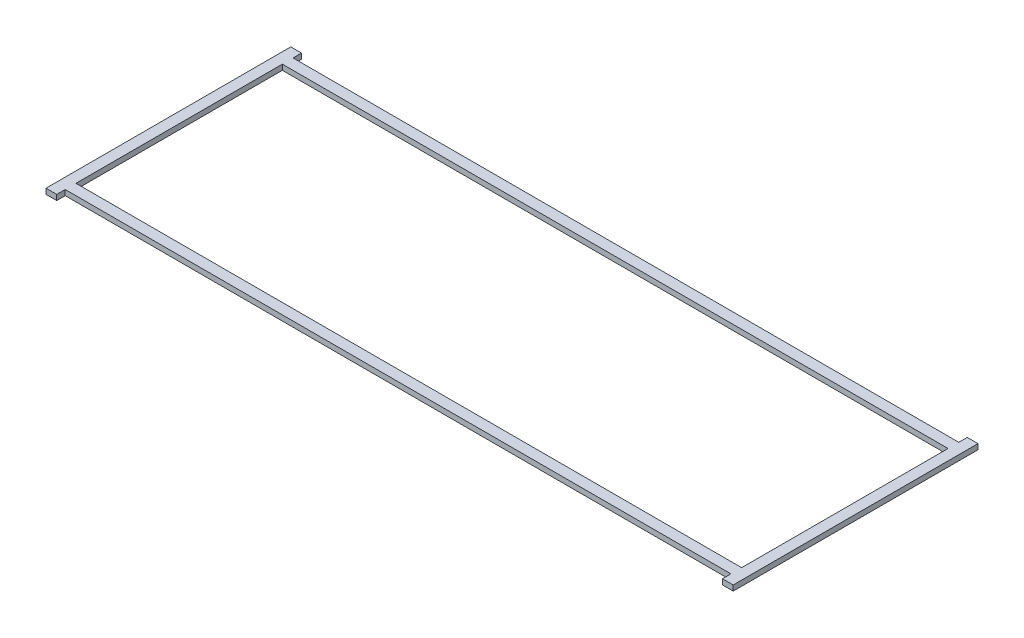
SolidWorks part; units mm, degrees
ref_plane "Front" through (0, 0, 0) normal (0, 0, 1) x (1, 0, 0)
ref_plane "Top" through (0, 0, 0) normal (0, 1, 0) x (1, 0, 0)
ref_plane "Right" through (0, 0, 0) normal (1, 0, 0) x (0, 0, -1)
sketch "Sketch1" plane through (0, 0, 0) normal (0, 1, 0) x (1, 0, 0)
  line L0 (196.85, 72.39) -> (203.2, 72.39)
  line L1 (-203.2, 72.39) -> (-196.85, 72.39)
  line L2 (-203.2, 72.39) -> (-203.2, -72.39)
  line L3 (-203.2, -72.39) -> (-196.85, -72.39)
  line L4 (203.2, 72.39) -> (203.2, -72.39)
  line L5 (-203.2, 72.39) -> (203.2, -72.39) construction
  line L6 (-203.2, -72.39) -> (203.2, 72.39) construction
  line L8 (-196.85, 72.39) -> (-196.85, 67.3799)
  line L9 (-196.85, 67.3799) -> (196.85, 67.3799)
  line L10 (196.85, 72.39) -> (196.85, 67.3799)
  line L12 (-196.85, -72.39) -> (-196.85, -67.3798)
  line L13 (-196.85, -67.3798) -> (196.85, -67.3798)
  line L14 (196.85, -72.39) -> (196.85, -67.3798)
  line L15 (196.85, -72.39) -> (203.2, -72.39)
  line L17 (-196.85, -61.0299) -> (196.85, -61.0299)
  line L18 (-196.85, -61.0299) -> (-196.85, 61.0299)
  line L19 (-196.85, 61.0299) -> (196.85, 61.0299)
  line L20 (196.85, -61.0299) -> (196.85, 61.0299)
  line L21 (-196.85, -61.0299) -> (196.85, 61.0299) construction
  line L22 (-196.85, 61.0299) -> (196.85, -61.0299) construction
  point P0 (0, 0)
  point P14 (0, 0)
  dimension "D1" = 406.4
  dimension "D2" = 144.78
  dimension "D3" = 6.35
  dimension "D4" = 6.35
  dimension "D5" = 134.7597
  dimension "D6" = 6.35
  dimension "D7" = 6.35
extrude "Boss-Extrude1" add sketch "Sketch1" along normal blind 3.175
equation "\"D2@Sketch1\"=(4.87075-.25) + 3 * ( 0.25 + ( 6 / 64 ) + 0.016 )"
equation "\"D5@Sketch1\"=(4.47625-.25) + 3 * ( 0.25 + ( 6 / 64 ) + 0.016 )"
